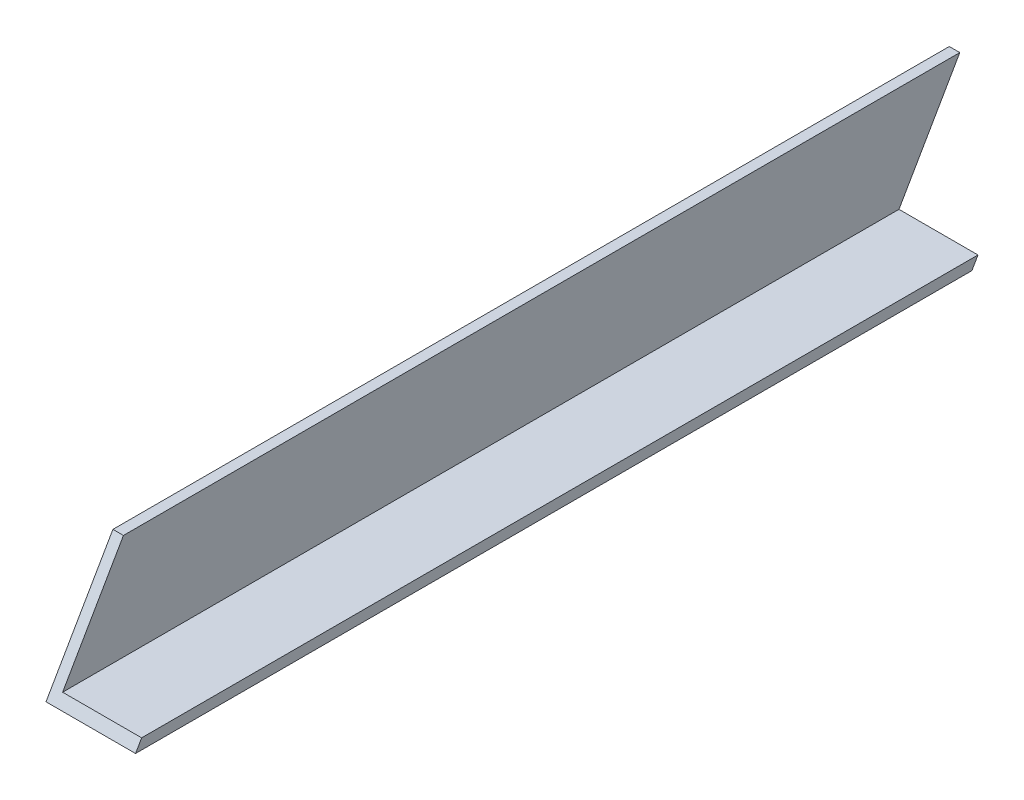
SolidWorks part; units mm, degrees
ref_plane "Front Plane" through (0, 0, 0) normal (0, 0, 1) x (1, 0, 0)
ref_plane "Top Plane" through (0, 0, 0) normal (0, 1, 0) x (1, 0, 0)
ref_plane "Right Plane" through (0, 0, 0) normal (1, 0, 0) x (0, 0, -1)
sketch "Sketch1" plane through (0, 0, 0) normal (0, 0, 1) x (1, 0, 0)
  line L0 (0, 0) -> (0, 22)
  line L1 (0, 22) -> (2, 22)
  line L2 (2, 22) -> (2, 2)
  line L3 (2, 2) -> (17, 2)
  line L4 (17, 2) -> (17, 0)
  line L5 (17, 0) -> (0, 0)
  dimension "D1" = 22
  dimension "D2" = 17
  dimension "D3" = 2
  dimension "D4" = 2
extrude "Boss-Extrude1" add sketch "Sketch1" along normal blind 200
sketch "Sketch2" plane through (2, 0, 0) normal (1, 0, 0) x (0, 0, -1)
  line L0 (-200, 22) -> (-200, 0)
  line L1 (-200, 0) -> (-187.2983, 22)
  line L2 (-200, 22) -> (0, 22) construction
  line L3 (-187.2983, 22) -> (-200, 22)
  line L4 (0, 22) -> (-28.527, 22)
  line L5 (-28.527, 22) -> (-41.2287, 0)
  line L6 (-200, 0) -> (0, 0) construction
  line L7 (-41.2287, 0) -> (0, 0)
  line L8 (0, 0) -> (0, 22)
  dimension "D1" = 30
  dimension "D2" = 137.5
extrude "Cut-Extrude1" cut sketch "Sketch2" along normal through all both and the other way through all
